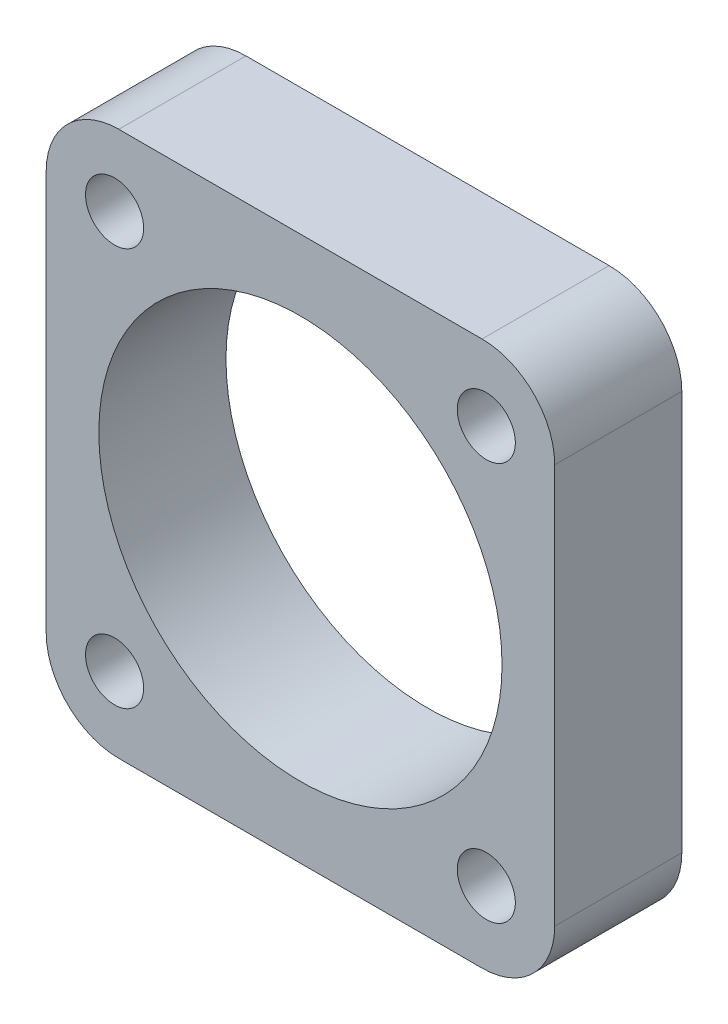
SolidWorks part; units mm, degrees
ref_plane "Front Plane" through (0, 0, 0) normal (0, 0, 1) x (1, 0, 0)
ref_plane "Top Plane" through (0, 0, 0) normal (0, 1, 0) x (1, 0, 0)
ref_plane "Right Plane" through (0, 0, 0) normal (1, 0, 0) x (0, 0, -1)
sketch "Sketch1" plane through (0, 0, 0) normal (0, 0, 1) x (1, 0, 0)
  line L0 (0, 15) -> (0, -15) construction
  line L1 (-14, 15) -> (14, 15)
  line L2 (-14, 15) -> (-14, -15)
  line L3 (-14, -15) -> (14, -15)
  line L4 (14, 15) -> (14, -15)
  line L5 (-14, 15) -> (14, -15) construction
  line L6 (-14, -15) -> (14, 15) construction
  line L7 (-10.2348, 7.7904) -> (-7.4848, 9.3781)
  line L8 (-7.4848, 9.3781) -> (-7.4848, 12.5535)
  line L9 (-7.4848, 12.5535) -> (-10.2348, 14.1413)
  line L10 (-10.2348, 14.1413) -> (-12.9848, 12.5535)
  line L11 (-12.9848, 12.5535) -> (-12.9848, 9.3781)
  line L12 (-12.9848, 9.3781) -> (-10.2348, 7.7904)
  line L19 (12.9848, 9.3781) -> (10.2348, 7.7904)
  line L20 (12.9848, 12.5535) -> (12.9848, 9.3781)
  line L21 (10.2348, 14.1413) -> (12.9848, 12.5535)
  line L22 (7.4848, 12.5535) -> (10.2348, 14.1413)
  line L23 (7.4848, 9.3781) -> (7.4848, 12.5535)
  line L24 (10.2348, 7.7904) -> (7.4848, 9.3781)
  line L25 (14, 0) -> (-14, 0) construction
  line L26 (-10.2348, -7.7904) -> (-7.4848, -9.3781)
  line L27 (-7.4848, -9.3781) -> (-7.4848, -12.5535)
  line L28 (-7.4848, -12.5535) -> (-10.2348, -14.1413)
  line L29 (-10.2348, -14.1413) -> (-12.9848, -12.5535)
  line L30 (-12.9848, -12.5535) -> (-12.9848, -9.3781)
  line L31 (-12.9848, -9.3781) -> (-10.2348, -7.7904)
  line L32 (12.9848, -9.3781) -> (10.2348, -7.7904)
  line L33 (12.9848, -12.5535) -> (12.9848, -9.3781)
  line L34 (10.2348, -14.1413) -> (12.9848, -12.5535)
  line L35 (7.4848, -12.5535) -> (10.2348, -14.1413)
  line L36 (7.4848, -9.3781) -> (7.4848, -12.5535)
  line L37 (10.2348, -7.7904) -> (7.4848, -9.3781)
  circle A0 centre (0, 0) radius 11.1
  circle A1 centre (-10.2348, 10.9658) radius 1.6
  circle A2 centre (-10.2348, 10.9658) radius 2.75 construction
  circle A4 centre (10.2348, 10.9658) radius 1.6
  circle A5 centre (-10.2348, -10.9658) radius 1.6
  circle A6 centre (10.2348, -10.9658) radius 1.6
  dimension "D1" = 22.2
  dimension "D4" = 3.2
  dimension "D2" = 28
  dimension "D3" = 30
  dimension "D5" = 5.5
  dimension "D6" = 15
extrude "Boss-Extrude1" add sketch "Sketch1" along normal blind 7 contours L4 L1 L2 L3 A0 L37 L32 L33 L34 L35 L36 L12 L11 L10 L9 L8 L7 L19 L24 L23 L22 L21 L20 L30 L31 L26 L27 L28 L29 | L24 L19 L20 L21 L22 L23 A4 | L11 L12 L7 L8 L9 L10 A1 | L31 L30 L29 L28 L27 L26 A5 | L32 L37 L36 L35 L34 L33 A6 region at (0, 14.5896, 0) region at (-11.5678, 8.657, 0) region at (11.5678, 8.657, 0) region at (-8.9018, -8.657, 0) region at (12.9008, -10.9658, 0)
fillet "Fillet1" [suppressed] radius 10
extrude "Cut-Extrude3" cut sketch "Sketch1<4>" along normal blind 3 contours L24 L19 L20 L21 L22 L23 A4 | L11 L12 L7 L8 L9 L10 A1 | L31 L30 L29 L28 L27 L26 A5 | L32 L37 L36 L35 L34 L33 A6 region at (-11.5678, 8.657, 0) region at (11.5678, 8.657, 0) region at (-8.9018, -8.657, 0) region at (12.9008, -10.9658, 0)
sketch "Sketch1<4>" plane through (0, 0, 0) normal (0, 0, 1) x (1, 0, 0) same geometry as "Sketch1"
fillet "Fillet5" radius 4 4 edges at (-14, 15, 3.5) (-14, -15, 3.5) (14, 15, 3.5) (14, -15, 3.5)
